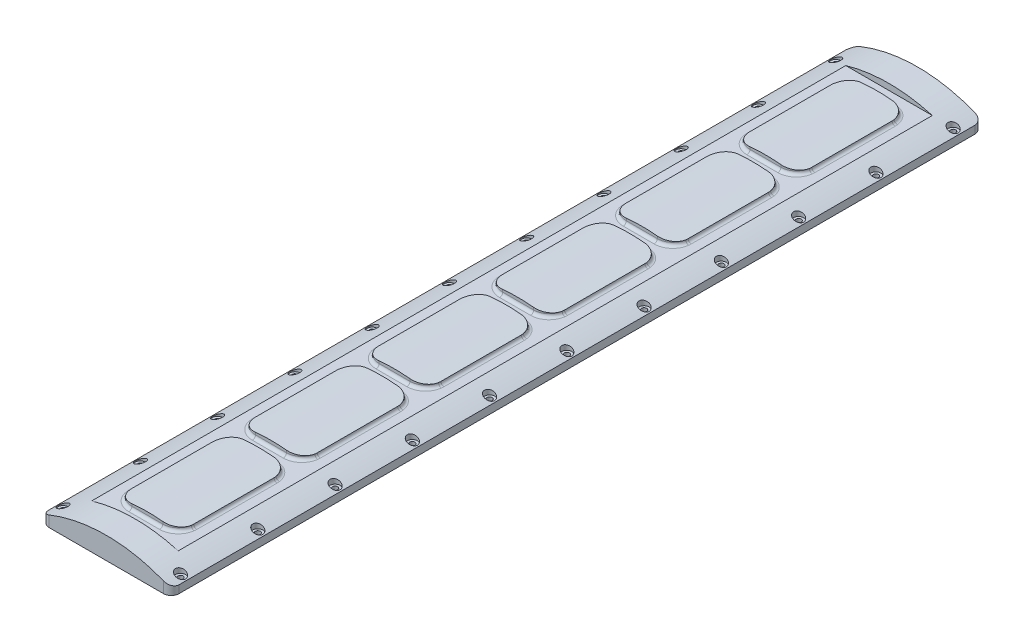
SolidWorks part; units mm, degrees
ref_plane "Front Plane" through (0, 0, 0) normal (0, 0, 1) x (1, 0, 0)
ref_plane "Top Plane" through (0, 0, 0) normal (0, 1, 0) x (1, 0, 0)
ref_plane "Right Plane" through (0, 0, 0) normal (1, 0, 0) x (0, 0, -1)
sketch "Sketch1" plane through (0, 0, 0) normal (0, 0, 1) x (1, 0, 0)
  line L1 (-42, 5) -> (42, 5) construction
  line L2 (-42, 5) -> (-42, 0)
  line L3 (-42, 0) -> (42, 0)
  line L4 (42, 5) -> (42, 0)
  arc A0 (-42, 5) -> (42, 5) centre (0, -85.7524) cw
  point P4 (0, 0)
  dimension "D3" = 100
  dimension "D1" = 84
  dimension "D2" = 5
extrude "Boss-Extrude1" add sketch "Sketch1" along normal mid plane 525
sketch "Sketch2" plane through (0, 0, 0) normal (1, 0, 0) x (0, 0, -1)
  line L0 (262.5, 14.2476) -> (-262.5, 14.2476) construction
  line L1 (-4, 10.2476) -> (4, 10.2476)
  line L2 (-4, 10.2476) -> (-4, 18.2476)
  line L3 (-4, 18.2476) -> (4, 18.2476)
  line L4 (4, 10.2476) -> (4, 18.2476)
  line L5 (-4, 10.2476) -> (4, 18.2476) construction
  line L6 (-4, 18.2476) -> (4, 10.2476) construction
  point P0 (0, 14.2476)
  dimension "D1" = 8
  dimension "D2" = 8
extrude "Cut-Extrude1" cut sketch "Sketch2" against normal mid plane 525
pattern_linear "LPattern1" count 4 spacing 80 along (0, 0, -1) count 4 spacing 80 along (0, 0, 1) of "Cut-Extrude1"
sketch "Sketch3" plane through (0, 10.2476, 0) normal (0, 1, 0) x (1, 0, 0)
  line L1 (-28, 244) -> (-20, 244)
  line L2 (-28, 244) -> (-28, -244)
  line L3 (-28, -244) -> (-20, -244)
  line L4 (-20, 244) -> (-20, -244)
  line L5 (-28, 244) -> (28, 244) construction
  line L6 (20, 244) -> (28, 244)
  line L7 (20, 244) -> (20, -244)
  line L8 (20, -244) -> (28, -244)
  line L9 (28, 244) -> (28, -244)
  line L10 (-28, -244) -> (28, -244) construction
  line L11 (28, -244) -> (-28, -244) construction
  dimension "D1" = 8
  dimension "D2" = 8
extrude "Cut-Extrude2" cut sketch "Sketch3" along normal blind 525
fillet "Fillet3" radius 10 24 edges at (20, 11.2374, -4) (-20, 11.2374, -4) (-20, 11.2374, 4) (20, 11.2374, 4) (20, 11.2374, -164) (20, 11.2374, -156) (20, 11.2374, -84) (20, 11.2374, -76) (-20, 11.2374, -164) (-20, 11.2374, -156) (-20, 11.2374, -84) (-20, 11.2374, -76) (-20, 11.2374, 76) (20, 11.2374, -236) (-20, 11.2374, -236) (20, 11.2374, 76) (20, 11.2374, 84) (-20, 11.2374, 84) (-20, 11.2374, 156) (20, 11.2374, 156) (-20, 11.2374, 236) (20, 11.2374, 164) (-20, 11.2374, 164) (20, 11.2374, 236)
fillet "Fillet4" radius 2 36 edges at (17.0711, 10.2476, -166.9289) (17.0711, 10.2476, -233.0711) (0, 10.2476, -236) (-17.0711, 10.2476, -233.0711) (-17.0711, 10.2476, -166.9289) (0, 10.2476, -164) (17.0711, 10.2476, -86.9289) (17.0711, 10.2476, -153.0711) (0, 10.2476, -156) (-17.0711, 10.2476, -153.0711) (-17.0711, 10.2476, -86.9289) (0, 10.2476, -84) (17.0711, 10.2476, 233.0711) (17.0711, 10.2476, 166.9289) (0, 10.2476, 164) (-17.0711, 10.2476, 166.9289) (-17.0711, 10.2476, 233.0711) (0, 10.2476, 236) (17.0711, 10.2476, 86.9289) (0, 10.2476, 84) (-17.0711, 10.2476, 86.9289) (-17.0711, 10.2476, 153.0711) (0, 10.2476, 156) (17.0711, 10.2476, 6.9289) (0, 10.2476, 4) (-17.0711, 10.2476, 6.9289) (-17.0711, 10.2476, 73.0711) (0, 10.2476, 76) (17.0711, 10.2476, -6.9289) (17.0711, 10.2476, -73.0711) (0, 10.2476, -76) (-17.0711, 10.2476, -73.0711) (-17.0711, 10.2476, -6.9289) (0, 10.2476, -4) (17.0711, 10.2476, 73.0711) (17.0711, 10.2476, 153.0711)
fillet "Fillet5" radius 5 4 edges at (42, 2.5, -262.5) (-42, 2.5, 262.5) (-42, 2.5, -262.5) (42, 2.5, 262.5)
ref_plane "Plane1" through (0, 8, 0) normal (0, 1, 0) x (1, 0, 0)
hole_wizard "CBORE for M3 Hex Socket Head Cap Screw1" positions "Sketch6" profile "Sketch7" counterbore size "M3" standard "ISO" end condition through all
sketch "Sketch6" plane through (0, 8, 0) normal (0, 1, 0) x (1, 0, 0)
  line L0 (-37, -262.5) -> (37, -262.5) construction
  line L1 (42, -257.5) -> (42, 257.5) construction
  line L2 (0, -7.8362) -> (0, 7.8362) construction
  point P5 (38, -252.5)
  point P26 (38, -202.5)
  point P27 (38, -152.5)
  point P28 (38, -102.5)
  point P29 (38, -52.5)
  point P30 (38, -2.5)
  point P31 (38, 47.5)
  point P32 (38, 97.5)
  point P33 (38, 147.5)
  point P34 (38, 197.5)
  point P35 (38, 247.5)
  point P38 (-38, 147.5)
  point P39 (-38, 97.5)
  point P40 (-38, 47.5)
  point P41 (-38, -2.5)
  point P42 (-38, -152.5)
  point P43 (-38, -252.5)
  point P44 (-38, 247.5)
  point P45 (-38, 197.5)
  point P46 (-38, -52.5)
  point P47 (-38, -102.5)
  point P48 (-38, -202.5)
  dimension "D1" = 10
  dimension "D2" = 4
  dimension "D3" = 11
sketch "Sketch7" plane through (38, 8, 252.5) normal (1, 0, 0) x (0, 0, 1)
  line L0 (0, 0) -> (0, 8)
  line L1 (0, 8) -> (1.7, 8)
  line L3 (1.7, 8) -> (1.7, 3.4)
  line L4 (1.7, 3.4) -> (3.25, 3.4)
  line L5 (3.25, 3.4) -> (3.25, 0)
  line L7 (3.25, 0) -> (0, 0)
  line L11 (0, -6.35) -> (0, 107.95) construction
  dimension "Thru Hole Dia." = 3.4
  dimension "Thru Hole Depth" = 8
  dimension "C'Bore Dia." = 6.5
  dimension "C'Bore Depth" = 3.4
